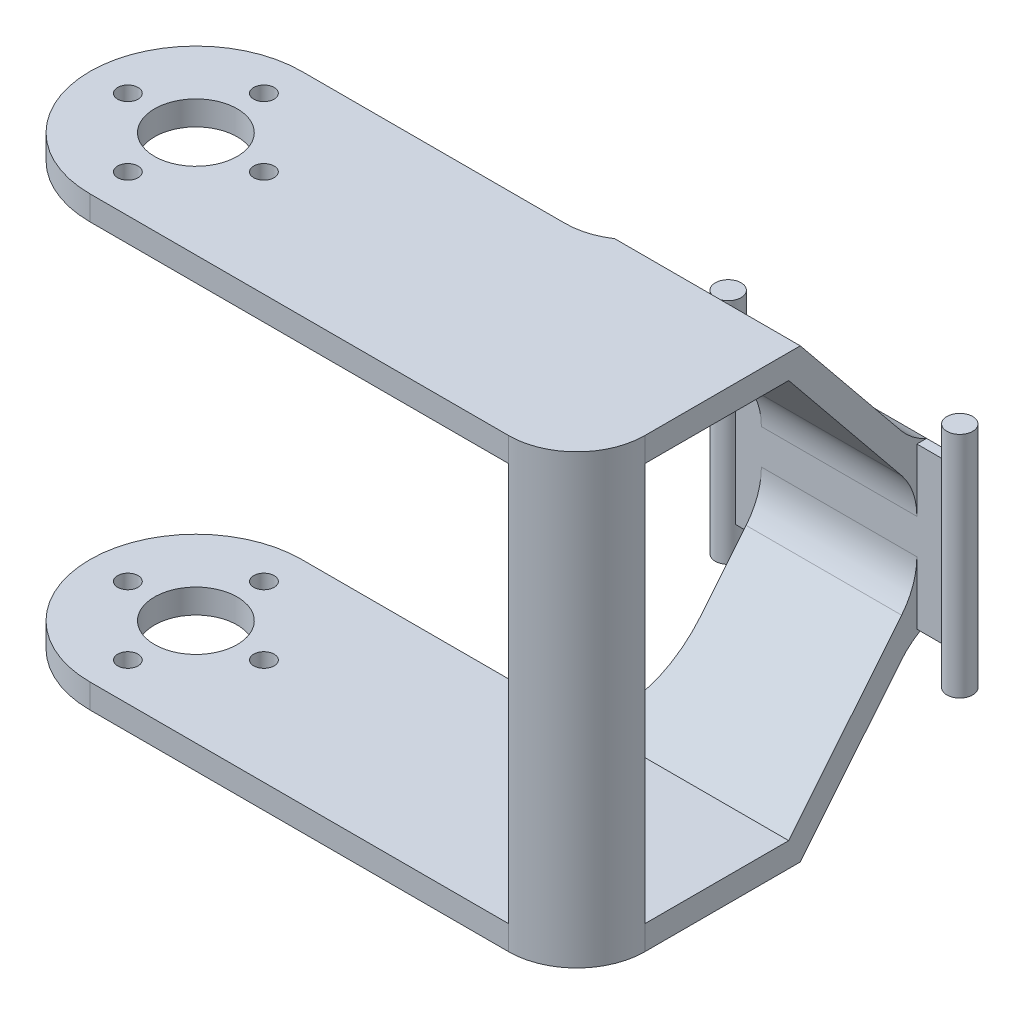
SolidWorks part; units mm, degrees
ref_plane "Front Plane" through (0, 0, 0) normal (0, 0, 1) x (1, 0, 0)
ref_plane "Top Plane" through (0, 0, 0) normal (0, 1, 0) x (1, 0, 0)
ref_plane "Right Plane" through (0, 0, 0) normal (1, 0, 0) x (0, 0, -1)
sketch "Sketch1" plane through (0, 0, 0) normal (0, 1, 0) x (1, 0, 0)
  line L1 (11.915, 0.5) -> (-11.915, 0.5)
  line L2 (11.915, 0.5) -> (11.915, -0.5)
  line L3 (11.915, -0.5) -> (-11.915, -0.5)
  line L4 (-11.915, 0.5) -> (-11.915, -0.5)
  line L5 (11.915, 0.5) -> (-11.915, -0.5) construction
  line L6 (11.915, -0.5) -> (-11.915, 0.5) construction
  point P0 (0, 0)
  dimension "D1" = 23.83
  dimension "D3" = 1
extrude "Boss-Extrude1" add sketch "Sketch1" along normal blind 16.5
ref_plane "Plane1" through (0, 8.25, 0) normal (0, 1, 0) x (1, 0, 0)
sketch "Sketch2" plane through (0, 8.25, 0) normal (0, 1, 0) x (1, 0, 0)
  line L0 (11.915, -0.5) -> (11.915, 0.5) construction
  line L1 (-11.915, 0.5) -> (-11.915, -0.5) construction
  line L2 (11.915, -0.5) -> (11.915, 0.5) construction
  line L3 (-11.915, 0.5) -> (-11.915, -0.5) construction
  circle A0 centre (-11.915, 0) radius 1.325
  circle A1 centre (11.915, 0) radius 1.325
  dimension "D1" = 2.65
extrude "Boss-Extrude2" add sketch "Sketch2" along normal mid plane 23.5
sketch "Sketch3" plane through (0, 16.5, 0) normal (0, 1, 0) x (1, 0, 0)
  line L0 (-10.688, -0.5) -> (10.688, -0.5) construction
  line L1 (-7.5, -0.5) -> (7.5, -0.5)
  line L2 (-7.5, -0.5) -> (-7.5, -26.5)
  line L3 (-7.5, -26.5) -> (7.5, -26.5)
  line L4 (7.5, -0.5) -> (7.5, -26.5)
  line L5 (0, -1000) -> (0, 49000) construction
  line L6 (-7.5, -26.5) -> (-32.5, -26.5)
  line L7 (-7.5, -26.5) -> (-7.5, -3.5)
  line L8 (-7.5, -3.5) -> (-32.5, -3.5)
  line L9 (-32.5, -26.5) -> (-32.5, -3.5)
  line L11 (-4.5, -3.5) -> (4.5, -3.5)
  line L12 (4.5, -3.5) -> (4.5, -23.5)
  line L13 (-4.5, -23.5) -> (4.5, -23.5)
  line L14 (-10.5, -23.5) -> (-29.5, -23.5)
  line L16 (-10.5, -6.5) -> (-29.5, -6.5)
  line L18 (-29.5, -23.5) -> (-29.5, -6.5) construction
  line L19 (-10.5, -23.5) -> (-10.5, -6.5) construction
  line L20 (-4.5, -3.5) -> (-4.5, -23.5) construction
  line L21 (-4.5, -3.5) -> (-4.5, -6.5)
  line L22 (-4.5, -6.5) -> (-10.5, -6.5)
  line L23 (-4.5, -23.5) -> (-10.5, -23.5)
  line L24 (-18.5, -6.5) -> (-18.5, -23.5)
  circle A0 centre (-32.5, -15) radius 11.5
  circle A1 centre (-32.5, -15) radius 4.25
  circle A2 centre (-32.5, -15) radius 7 construction
  circle A3 centre (-32.5, -8) radius 1.05
  circle A4 centre (-25.5, -15) radius 1.05
  circle A5 centre (-32.5, -22) radius 1.05
  circle A6 centre (-39.5, -15) radius 1.05
  point P10 (0, -0.5)
  line M14 (-10.688, -0.5) -> (10.688, -0.5)
  dimension "D5" = 8.5
  dimension "D6" = 14
  dimension "D7" = 2.1
  dimension "D1" = 15
  dimension "D2" = 26
  dimension "D3" = 23
  dimension "D4" = 25
  dimension "D9" = 14
  dimension "D8" = 3
extrude "Boss-Extrude3" [suppressed] add sketch "Sketch3" against normal up to surface (18.5 mm away) contours L4 L2 L3 M14 | A0 L6 L2 L8 | A5 L9 A0 A3 A1 A4 | A5 L9 A1 A3 A0 A6 | A0 L16 L22 L2 L8 | A0 L6 L2 L23 L14
sketch "Sketch4" plane through (0, 0, 0) normal (1, 0, 0) x (0, 0, -1)
  line L0 (-0.5, 16.5) -> (-12.5, 31.25)
  line L1 (-12.5, 31.25) -> (-35.5, 31.25)
  line L2 (-35.5, 31.25) -> (-35.5, 28.75)
  line L3 (-35.5, 28.75) -> (-13.6889, 28.75)
  line L4 (-13.6889, 28.75) -> (-0.5, 12.5386)
  line L5 (-0.5, 16.5) -> (-0.5, 0) construction
  line L6 (-0.5, 16.5) -> (-0.5, 0)
  line L7 (-0.5, 0) -> (-12.5, -14.75)
  line L8 (-12.5, -14.75) -> (-35.5, -14.75)
  line L9 (-35.5, -14.75) -> (-35.5, -12.25)
  line L10 (-35.5, -12.25) -> (-13.6889, -12.25)
  line L11 (-13.6889, -12.25) -> (-0.5, 3.9614)
  line L12 (-1000.5, 8.25) -> (48999.5, 8.25) construction
  line L13 (-35.5, 28.75) -> (-35.5, -12.25) construction
  point P3 (-35.5, 8.25)
  point P20 (-0.5, 8.25)
  dimension "D1" = 2.5
  dimension "D2" = 41
  dimension "D3" = 23
  dimension "D4" = 2.5
  dimension "D5" = 35
  dimension "D6" = 2.5
extrude "Boss-Extrude4" add sketch "Sketch4" along normal mid plane 16 contours L6 L0 L1 L2 L3 L4 | L11 L10 L9 L8 L7 L6
sketch "Sketch5" plane through (-8, 0, 0) normal (-1, 0, 0) x (0, 0, 1)
  line L1 (35.5, 31.25) -> (13.6889, 31.25)
  line L2 (35.5, 31.25) -> (35.5, 28.75)
  line L3 (35.5, 28.75) -> (13.6889, 28.75)
  line L4 (13.6889, 31.25) -> (13.6889, 28.75)
  line L5 (35.5, -14.75) -> (13.6889, -14.75)
  line L6 (35.5, -14.75) -> (35.5, -12.25)
  line L7 (35.5, -12.25) -> (13.6889, -12.25)
  line L8 (13.6889, -14.75) -> (13.6889, -12.25)
extrude "Boss-Extrude5" add sketch "Sketch5" along normal blind 45
sketch "Sketch6" plane through (0, 31.25, 0) normal (0, 1, 0) x (1, 0, 0)
  line L0 (-42.0945, -13.6889) -> (-42.0945, -35.5) construction
  line L1 (-53, -13.6889) -> (-8, -13.6889) construction
  line L2 (8, -35.5) -> (-53, -35.5) construction
  line L3 (-53, -24.5945) -> (8, -24.5945) construction
  line L4 (-53, -35.5) -> (-53, -13.6889) construction
  line L5 (8, -12.5) -> (8, -35.5) construction
  line L6 (-42.0945, -13.6889) -> (-53, -13.6889)
  line L7 (-53, -13.6889) -> (-53, -35.5)
  line L8 (-53, -35.5) -> (-42.0945, -35.5)
  circle A0 centre (-42.0945, -24.5945) radius 10.9055
  circle A1 centre (-42.0945, -24.5945) radius 4.25
  circle A2 centre (-42.0945, -24.5945) radius 7 construction
  circle A3 centre (-42.0945, -17.5945) radius 1.05
  circle A4 centre (-35.0945, -24.5945) radius 1.05
  circle A5 centre (-42.0945, -31.5945) radius 1.05
  circle A6 centre (-49.0945, -24.5945) radius 1.05
  point P12 (-42.0945, -24.5945)
  line M9 (-8, -13.6889) -> (-53, -13.6889)
  line M10 (-53, -13.6889) -> (-53, -35.5)
  line M11 (-53, -35.5) -> (8, -35.5)
  dimension "D1" = 8.5
  dimension "D2" = 14
  dimension "D3" = 2.1
extrude "Cut-Extrude1" cut sketch "Sketch6" against normal through all contours A1 | A6 | A3 | A4 | A5 | A0 M9 M10 | A0 L7 M11
fillet "Fillet1" radius 7 4 edges at (-8, -13.5, 13.6889) (-8, 30, 13.6889) (8, -13.5, 35.5) (8, 30, 35.5)
fillet "Fillet2" radius 7 2 edges at (0, 3.9614, 0.5) (0, 12.5386, 0.5)
fillet "Fillet3" radius 7 2 edges at (0, 16.5, 0.5) (0, 0, 0.5)
sketch "Sketch8" plane through (0, -12.25, 0) normal (0, 1, 0) x (1, 0, 0)
  line L0 (-42.0945, -13.6889) -> (-15, -13.6889) construction
  line L1 (-42.0945, -13.6889) -> (-15, -13.6889)
  line L2 (8, -28.5) -> (5, -28.5)
  line L3 (1, -35.5) -> (1, -32.5)
  arc A0 (-15, -13.6889) -> (-8, -6.6889) centre (-15, -6.6889) ccw construction
  arc A1 (1, -35.5) -> (8, -28.5) centre (1, -28.5) ccw construction
  arc A2 (-15, -13.6889) -> (-8, -6.6889) centre (-15, -6.6889) ccw
  arc A3 (1, -35.5) -> (8, -28.5) centre (1, -28.5) ccw
  circle A4 centre (-1.5277, -25.9723) radius 7
  arc M10 (1, -35.5) -> (8, -28.5) centre (1, -28.5) ccw
  dimension "D1" = 3
extrude "Boss-Extrude6" add sketch "Sketch8" along normal up to surface (41 mm away) contours A4 L3 L2 M10 up to face at (-42.0945, 28.75, 28.8445)
equation "\"D4@Sketch4\"=\"D1@Sketch4\""
equation "\"D6@Sketch4\"=\"D1@Sketch4\""
